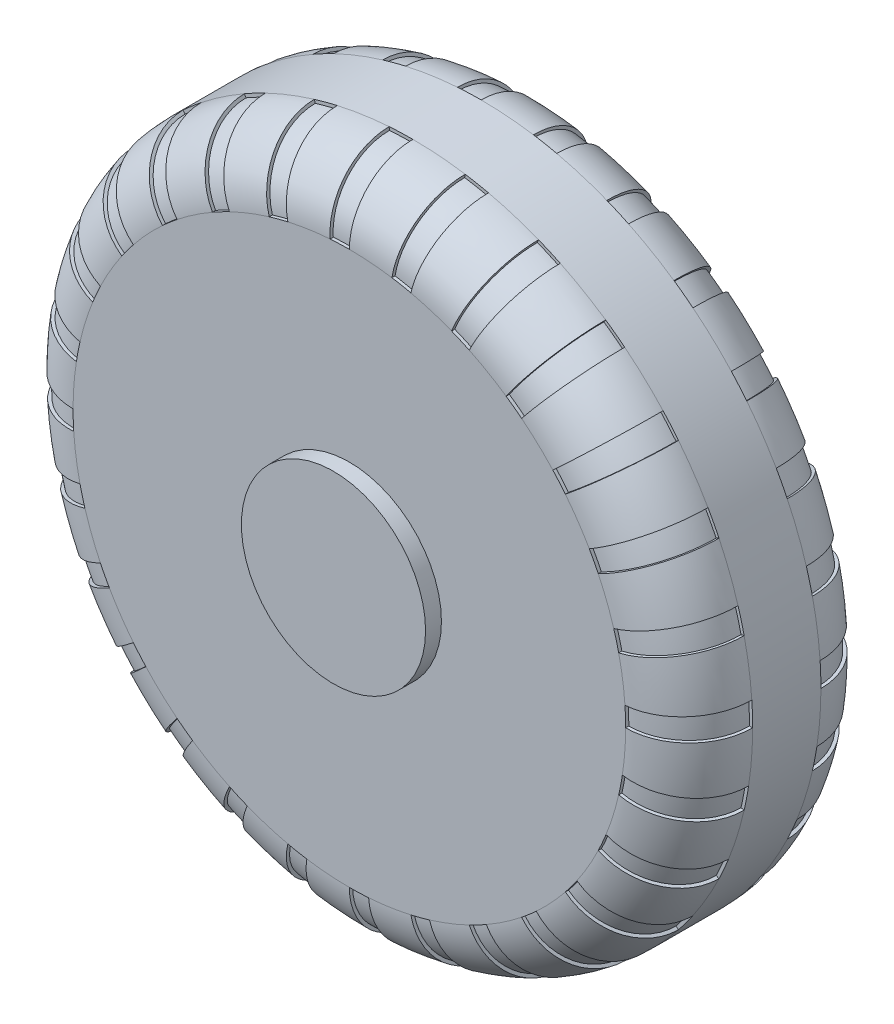
SolidWorks part; units mm, degrees
ref_plane "정면" through (0, 0, 0) normal (0, 0, 1) x (1, 0, 0)
ref_plane "윗면" through (0, 0, 0) normal (0, 1, 0) x (1, 0, 0)
ref_plane "우측면" through (0, 0, 0) normal (1, 0, 0) x (0, 0, -1)
sketch "스케치1" plane through (0, 0, 0) normal (0, 0, 1) x (1, 0, 0)
  circle A0 centre (0, 0) radius 107
  dimension "D1" = 214
extrude "보스-돌출1" add sketch "스케치1" along normal blind 30.75 and the other way blind 30.75
fillet "필렛1" radius 20 2 edges at (107, 0, -30.75) (107, 0, 30.75)
sketch "스케치2" plane through (0, 0, 0) normal (1, 0, 0) x (0, 0, -1)
  line L0 (29.75, 87) -> (30.75, 87)
  line L1 (10.75, 106) -> (10.75, 107)
  line L2 (49.5458, 0) -> (-49.5458, 0) construction
  arc A0 (30.75, 87) -> (10.75, 107) centre (10.75, 87) ccw construction
  arc A1 (30.75, 87) -> (10.75, 107) centre (10.75, 87) ccw
  arc A2 (29.75, 87) -> (10.75, 106) centre (10.75, 87) ccw
  point P10 (0, 0)
  dimension "D1" = 1
revolve "컷-회전1" cut sketch "스케치2" angle 4 about L2
pattern_circular "원형 패턴1" count 28 over 360 about axis through (0, 0, -30.75) along (0, 0, -1) of "컷-회전1"
mirror "대칭 복사2" about plane through (0, 0, 0) normal (0, 0, 1) of "원형 패턴1"
sketch "스케치3" plane through (0, 0, -30.75) normal (0, 0, -1) x (-1, 0, 0)
  circle A0 centre (0, 0) radius 29
  dimension "D1" = 58
extrude "보스-돌출2" add sketch "스케치3" along normal blind 23.5
sketch "스케치4" plane through (0, 0, 30.75) normal (0, 0, 1) x (1, 0, 0)
  circle A0 centre (0, 0) radius 29
  dimension "D1" = 58
extrude "보스-돌출3" add sketch "스케치4" along normal blind 5
sketch "스케치5" plane through (0, 0, -54.25) normal (0, 0, -1) x (-1, 0, 0)
  point P0 (0, 0)
